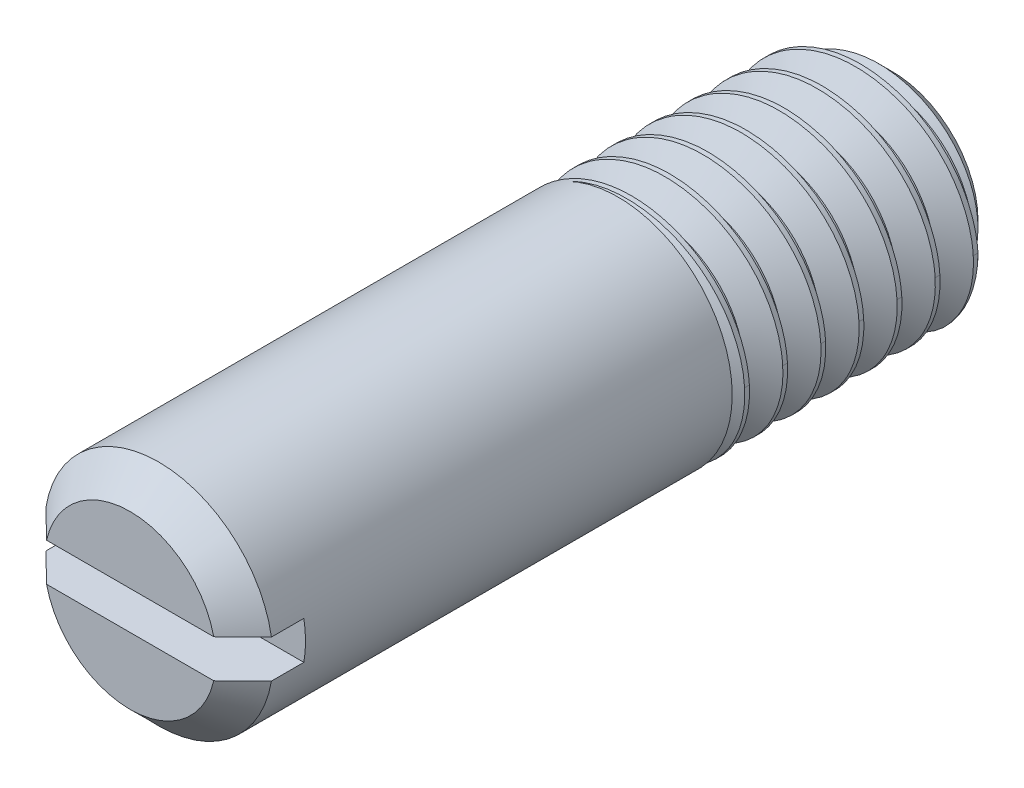
SolidWorks part; units mm, degrees
ref_plane "Front Plane" through (0, 0, 0) normal (0, 0, 1) x (1, 0, 0)
ref_plane "Top Plane" through (0, 0, 0) normal (0, 1, 0) x (1, 0, 0)
ref_plane "Right Plane" through (0, 0, 0) normal (1, 0, 0) x (0, 0, -1)
sketch "Sketch1" plane through (0, 0, 0) normal (1, 0, 0) x (0, 0, -1)
  line L0 (-6.4, 0) -> (3.6, 0) construction
  line L1 (3.6, 1.5) -> (3.6, -1.5) construction
  line L2 (-6.4, 0.25) -> (-6.4, -0.25) construction
  line L3 (-6.4, -0.25) -> (-5.6, -0.25) construction
  line L4 (3.6, 1.5) -> (3.1, 1.5) construction
  line L5 (3.1, 1.5) -> (0, 1.5) construction
  line L6 (0, 1.5) -> (-6.4, 1.5) construction
  point P5 (3.6, 0)
  point P9 (0, 0)
  dimension "Oall Length" = 10
  dimension "Thread Diameter" = 3
  dimension "Thread Length" = 3.6
  dimension "Slot Width n" = 0.5
  dimension "Slot Depth t" = 0.8
  dimension "Pitch" = 0.5
sketch "Sketch2" plane through (0, 0, 0) normal (1, 0, 0) x (0, 0, -1)
  line L0 (3.6, 0) -> (3.6, 1.5)
  line L1 (3.6, 1.5) -> (-6.4, 1.5)
  line L2 (-6.4, 1.5) -> (-6.4, 0)
  line L3 (-6.4, 0) -> (3.6, 0)
revolve "Revolve1" add sketch "Sketch2" angle 360 about L0
fillet "Chamfer2" radius 0.375 2 edges at (1.5, 0, 6.4) (1.5, 0, -3.6) profile chamfer
sketch "Sketch3" plane through (0, 0, 0) normal (1, 0, 0) x (0, 0, -1)
  line L0 (-5.6, -0.25) -> (-6.4, -0.25)
  line L1 (-6.4, -0.25) -> (-6.4, 0.25)
  line L2 (-6.4, 0.25) -> (-5.6, 0.25)
  line L3 (-5.6, 0.25) -> (-5.6, -0.25)
extrude "Cut-Extrude1" cut sketch "Sketch3" against normal through all both and the other way through all
sketch "Sketch4" plane through (0, 0, -3.6) normal (0, 0, -1) x (-1, 0, 0)
  circle A0 centre (0, 0) radius 1.5
curve "Helix/Spiral1" pitch 0.5 height 4.1 radius 1.5 centre (0, 0, -3.6) axis (0, 0, 1) start towards (0, 1, 0) parameters "pitch"=0.5
sketch "Sketch5" plane through (0, 0, 0) normal (1, 0, 0) x (0, 0, -1)
  line L0 (3.6, 1.5) -> (4.0375, 1.5) construction
  line L1 (4.0375, 1.5) -> (3.8187, 1.1211) construction
  line L2 (3.8187, 1.1211) -> (3.6, 1.5) construction
  line L3 (3.7875, 1.1752) -> (3.85, 1.1752) construction
  line L4 (3.8187, 1.1752) -> (3.8187, 1.5) construction
  line L5 (3.6937, 1.3376) -> (3.9437, 1.3376) construction
  line L6 (3.6, 1.5) -> (4.0375, 1.5)
  line L7 (4.0375, 1.5) -> (3.85, 1.1752)
  line L8 (3.85, 1.1752) -> (3.7875, 1.1752)
  line L9 (3.7875, 1.1752) -> (3.6, 1.5)
  point P7 (3.8187, 1.3376)
  dimension "D1" = 0.0625
  dimension "D2" = 0.25
sweep "Cut-Sweep1" cut profiles "Sketch5" path "Helix/Spiral1" align with end faces yes
sketch "Sketch6" plane through (0, 0, 0) normal (0, 0, 1) x (1, 0, 0)
  circle A1 centre (0, 0) radius 1.5
  circle A2 centre (0, 0) radius 1.5
  dimension "D1" = 0
extrude "Boss-Extrude2" add sketch "Sketch6" along normal blind 0.5
ref_axis "Center Axis 1" through (0, 0, -3.2302) along (0, 0, 1)
ref_plane "Contact Plane 1" through (0, 0, 0) normal (0, 0, 1) x (1, 0, 0)
equation "\"3..6250in\"=4.625"
equation "\"Slot Width n@Sketch1\"=\"Pitch@Sketch1\""
equation "\"Slot Depth t@Sketch1\"=\"Pitch@Sketch1\"*1.6"
equation "\"D1@Chamfer2\"=\"Pitch@Sketch1\"*.75"
equation "\"D1@Sketch5\"=\"Pitch@Sketch1\"*.125"
equation "\"D2@Sketch5\"=\"Pitch@Sketch1\"*.5"
equation "\"D3@Helix/Spiral1\"=\"Thread Length@Sketch1\"+(\"Pitch@Sketch1\")"
equation "\"D1@Boss-Extrude2\"=\"Pitch@Sketch1\""
